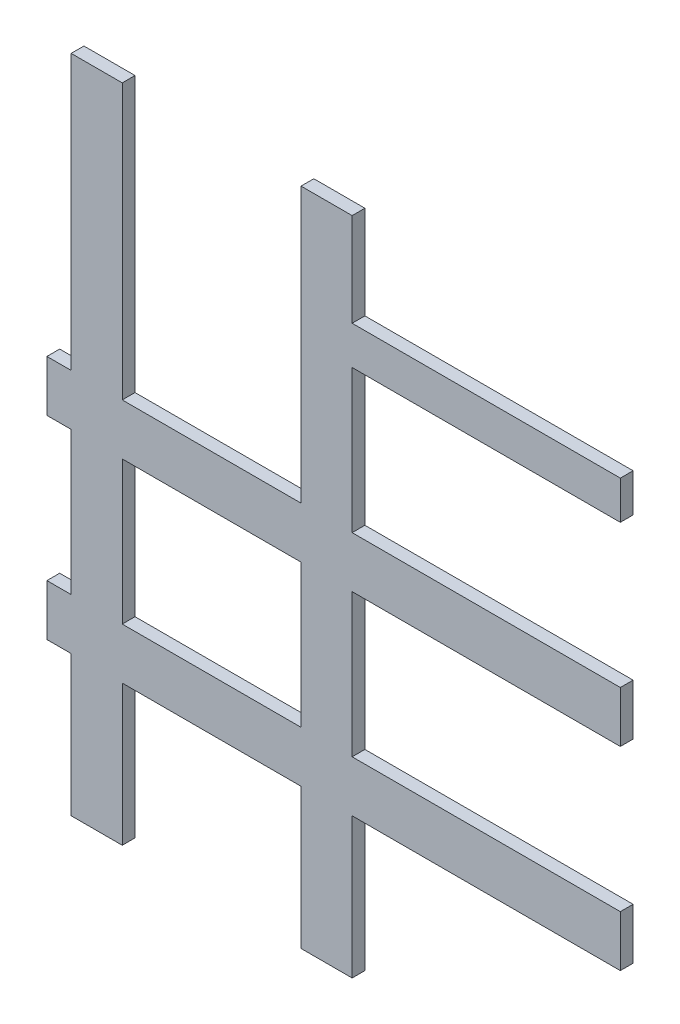
SolidWorks part; units mm, degrees
ref_plane "Piano frontale" through (0, 0, 0) normal (0, 0, 1) x (1, 0, 0)
ref_plane "Piano superiore" through (0, 0, 0) normal (0, 1, 0) x (1, 0, 0)
ref_plane "Piano destro" through (0, 0, 0) normal (1, 0, 0) x (0, 0, -1)
sketch "Schizzo1" plane through (0, 0, 0) normal (0, 0, 1) x (1, 0, 0)
  line L1 (0, 0) -> (4, 0)
  line L2 (0, 0) -> (0, 51.7)
  line L3 (0, 51.7) -> (4, 51.7)
  line L4 (4, 0) -> (4, 51.7)
  dimension "D1" = 4
  dimension "D2" = 51.7
extrude "Estrusione-Estrusione1" add sketch "Schizzo1" along normal blind 1
sketch "Schizzo2" plane through (4, 0, 0) normal (1, 0, 0) x (0, 0, -1)
  line L1 (-1, 0) -> (-1, 51.7) construction
  line L2 (0, 0) -> (0, 51.7) construction
  line L3 (-1, 30.2) -> (0, 30.2)
  line L4 (-1, 30.2) -> (-1, 26.2)
  line L5 (-1, 26.2) -> (0, 26.2)
  line L6 (0, 30.2) -> (0, 26.2)
  dimension "D2" = 4
extrude "Estrusione-Estrusione2" add sketch "Schizzo2" along normal blind 18 and the other way blind 5.9
sketch "Schizzo3" plane through (4, 0, 0) normal (1, 0, 0) x (0, 0, -1)
  line L1 (-1, 0) -> (-1, 26.2) construction
  line L2 (0, 0) -> (0, 26.2) construction
  line L3 (-1, 15) -> (0, 15)
  line L4 (-1, 15) -> (-1, 11)
  line L5 (-1, 11) -> (0, 11)
  line L6 (0, 15) -> (0, 11)
  dimension "D2" = 4
extrude "Estrusione-Estrusione3" add sketch "Schizzo3" along normal blind 18 and the other way blind 5.9
sketch "Schizzo4" plane through (0, 30.2, 0) normal (0, 1, 0) x (1, 0, 0)
  line L0 (4, 0) -> (22, 0) construction
  line L1 (22, -1) -> (18, -1)
  line L2 (22, -1) -> (22, 0)
  line L3 (22, 0) -> (18, 0)
  line L4 (18, -1) -> (18, 0)
  dimension "D1" = 4
extrude "Estrusione-Estrusione4" add sketch "Schizzo4" along normal blind 21.5 and the other way blind 30.2
sketch "Schizzo5" plane through (22, 0, 0) normal (1, 0, 0) x (0, 0, -1)
  line L0 (0, 0) -> (0, 51.7) construction
  line L1 (0, 44.3987) -> (-1, 44.3987)
  line L2 (0, 44.3987) -> (0, 41.3987)
  line L3 (0, 41.3987) -> (-1, 41.3987)
  line L4 (-1, 44.3987) -> (-1, 41.3987)
  line L5 (-1, 51.7) -> (-1, 0) construction
  dimension "D1" = 3
extrude "Estrusione-Estrusione5" add sketch "Schizzo5" along normal blind 21
sketch "Schizzo7" plane through (22, 0, 0) normal (1, 0, 0) x (0, 0, -1)
  line L1 (-1, 41.3987) -> (-1, 0) construction
  line L2 (0, 0) -> (0, 41.3987) construction
  line L3 (-1, 11) -> (0, 11)
  line L4 (-1, 11) -> (-1, 15)
  line L5 (-1, 15) -> (0, 15)
  line L6 (0, 11) -> (0, 15)
  dimension "D2" = 4
extrude "Estrusione-Estrusione6" add sketch "Schizzo7" along normal blind 21
sketch "Schizzo8" plane through (22, 0, 0) normal (1, 0, 0) x (0, 0, -1)
  line L1 (-1, 41.3987) -> (-1, 15) construction
  line L2 (0, 15) -> (0, 41.3987) construction
  line L3 (-1, 26.2) -> (0, 26.2)
  line L4 (-1, 26.2) -> (-1, 30.2)
  line L5 (-1, 30.2) -> (0, 30.2)
  line L6 (0, 26.2) -> (0, 30.2)
  dimension "D2" = 4
extrude "Estrusione-Estrusione7" add sketch "Schizzo8" along normal blind 21
